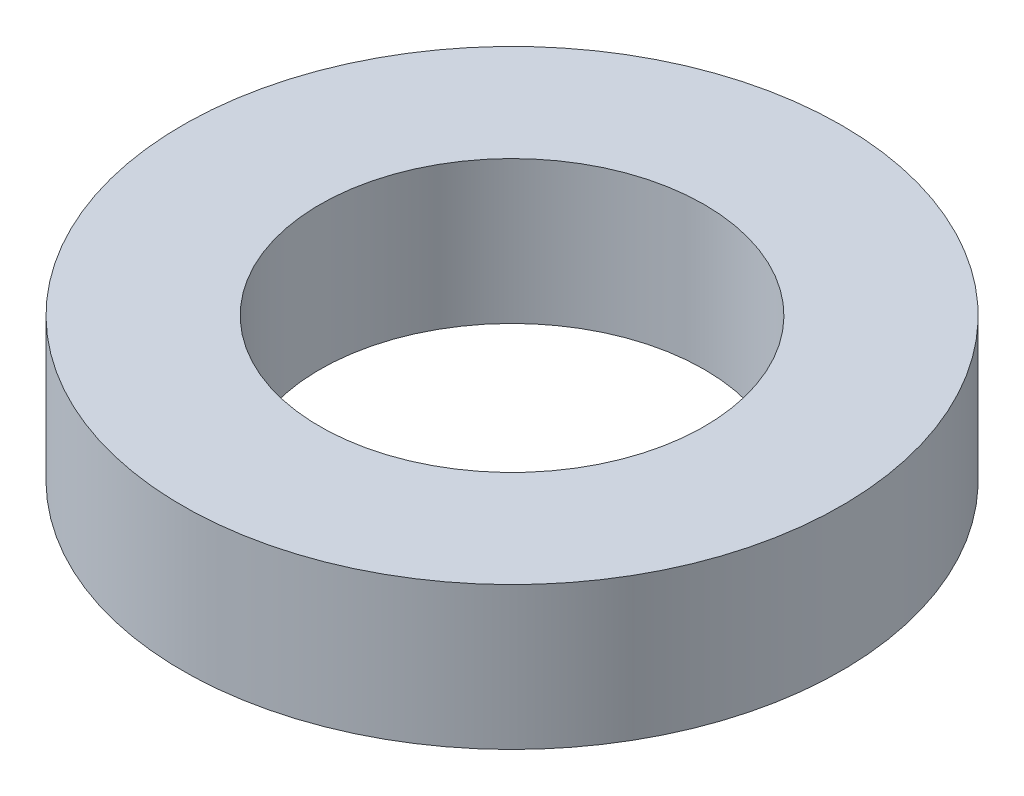
SolidWorks part; units mm, degrees
ref_plane "Front Plane" through (0, 0, 0) normal (0, 0, 1) x (1, 0, 0)
ref_plane "Top Plane" through (0, 0, 0) normal (0, 1, 0) x (1, 0, 0)
ref_plane "Right Plane" through (0, 0, 0) normal (1, 0, 0) x (0, 0, -1)
sketch "Sketch1" plane through (0, 0, 0) normal (0, 1, 0) x (1, 0, 0)
  circle A0 centre (0, 0) radius 30
  dimension "FLANGE_OD" = 60
extrude "Boss-Extrude1" add sketch "Sketch1" along normal blind 13
sketch "Sketch2" plane through (0, 0, 0) normal (0, 1, 0) x (1, 0, 0)
  circle A0 centre (0, 0) radius 17.5
  dimension "BORE_D" = 35
extrude "Cut-Extrude1" cut sketch "Sketch2" along normal through all
sketch "Sketch3" plane through (0, 13, 0) normal (0, 1, 0) x (1, 0, 0)
  circle A0 centre (0, 0) radius 12.4093 construction
  circle A1 centre (-12.4093, 0) radius 1.8686
  dimension "BOLT_D" = 3.7371
  dimension "BOLT_PCD" = 24.8185
extrude "Cut-Extrude2" cut sketch "Sketch3" against normal blind 9.4623 rebuild error yes
pattern_circular "CirPattern1" count 5 over 360 rebuild error yes
